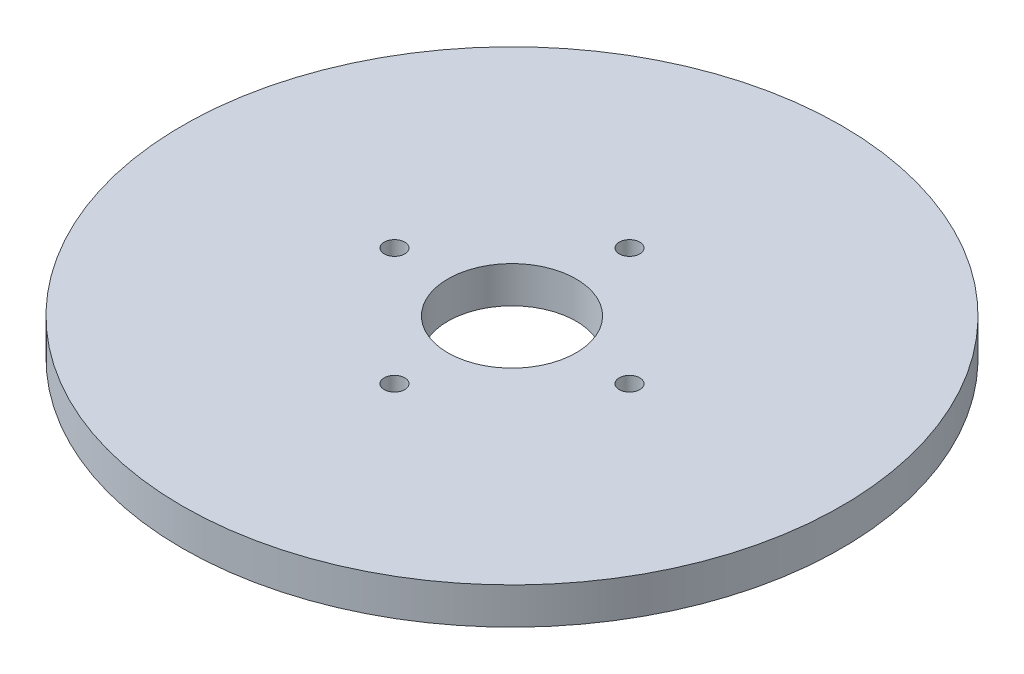
SolidWorks part; units mm, degrees
ref_plane "Front Plane" through (0, 0, 0) normal (0, 0, 1) x (1, 0, 0)
ref_plane "Top Plane" through (0, 0, 0) normal (0, 1, 0) x (1, 0, 0)
ref_plane "Right Plane" through (0, 0, 0) normal (1, 0, 0) x (0, 0, -1)
sketch "Sketch1" plane through (0, 0, 0) normal (0, 1, 0) x (1, 0, 0)
  circle A0 centre (0, 0) radius 90
  dimension "FLANGE_OD" = 180
extrude "Boss-Extrude1" add sketch "Sketch1" along normal blind 10
sketch "Sketch2" plane through (0, 0, 0) normal (0, 1, 0) x (1, 0, 0)
  circle A0 centre (0, 0) radius 17.5
  dimension "BORE_D" = 35
extrude "Cut-Extrude1" cut sketch "Sketch2" along normal through all
sketch "Sketch3" plane through (0, 10, 0) normal (0, 1, 0) x (1, 0, 0)
  circle A0 centre (0, 0) radius 32.096 construction
  circle A1 centre (-32.096, 0) radius 2.8081
  dimension "BOLT_D" = 5.6162
  dimension "BOLT_PCD" = 64.1919
extrude "Cut-Extrude2" cut sketch "Sketch3" against normal blind 6.0505
pattern_circular "CirPattern1" count 4 over 360 about axis through (0, 0, 0) along (0, 1, 0) of "Cut-Extrude2"
